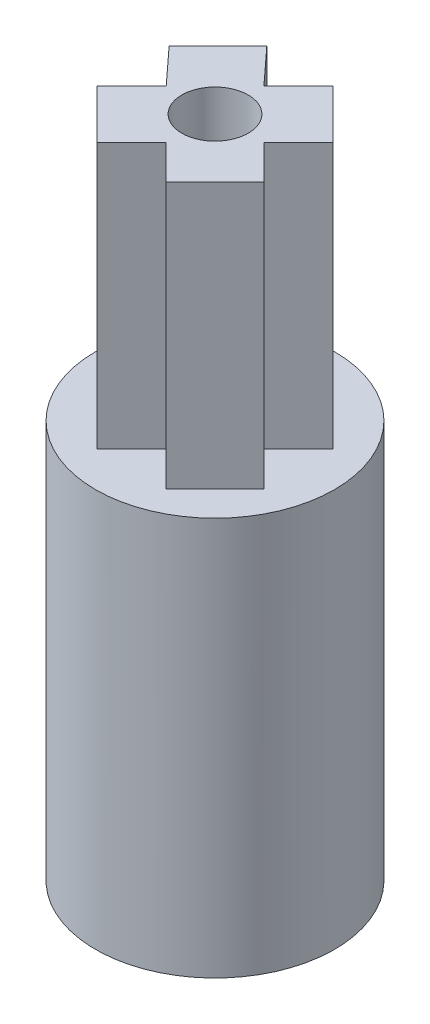
SolidWorks part; units mm, degrees
ref_plane "Front Plane" through (0, 0, 0) normal (0, 0, 1) x (1, 0, 0)
ref_plane "Top Plane" through (0, 0, 0) normal (0, 1, 0) x (1, 0, 0)
ref_plane "Right Plane" through (0, 0, 0) normal (1, 0, 0) x (0, 0, -1)
sketch "Sketch1" plane through (0, 0, 0) normal (0, 1, 0) x (1, 0, 0)
  circle A2 centre (0, 0) radius 5.715
  dimension "D3" = 11.43
extrude "Boss-Extrude1" add sketch "Sketch1" along normal blind 6.35
sketch "Sketch3" plane through (0, 0, 0) normal (0, -1, 0) x (-1, 0, 0)
  circle A0 centre (0, 0) radius 5.715
extrude "Boss-Extrude2" add sketch "Sketch3" along normal blind 12.7
sketch "Sketch4" plane through (0, -12.7, 0) normal (0, -1, 0) x (1, 0, 0)
  line L0 (0, 2.54) -> (-1.7961, 4.3361)
  line L1 (-2.54, -2.54) -> (2.54, -2.54) construction
  line L2 (-2.54, -2.54) -> (-2.54, 2.54) construction
  line L3 (-2.54, 2.54) -> (2.54, 2.54) construction
  line L4 (2.54, -2.54) -> (2.54, 2.54) construction
  line L5 (-2.54, -2.54) -> (2.54, 2.54) construction
  line L6 (-2.54, 2.54) -> (2.54, -2.54) construction
  line L7 (-2.54, 0) -> (-4.3361, 1.7961)
  line L8 (-4.3361, 1.7961) -> (-1.7961, 4.3361)
  line L9 (2.54, 0) -> (4.3361, -1.7961)
  line L10 (0, -2.54) -> (1.7961, -4.3361)
  line L11 (1.7961, -4.3361) -> (4.3361, -1.7961)
  line L12 (-2.54, 0) -> (-4.3361, -1.7961)
  line L13 (0, -2.54) -> (-1.7961, -4.3361)
  line L14 (-4.3361, -1.7961) -> (-1.7961, -4.3361)
  line L15 (2.54, 0) -> (4.3361, 1.7961)
  line L16 (1.7961, 4.3361) -> (4.3361, 1.7961)
  line L17 (0, 2.54) -> (1.7961, 4.3361)
  point P0 (0, 0)
  dimension "D1" = 2.54
  dimension "D2" = 5.08
  dimension "D3" = 5.08
  dimension "D4" = 8.6721
  dimension "D5" = 3.5921
  dimension "D6" = 3.5921
  dimension "D7" = 3.5921
  dimension "D8" = 3.5921
  dimension "D9" = 8.6721
  dimension "D10" = 0
  dimension "D11" = 3.5921
  dimension "D12" = 5.08
  dimension "D13" = 2.54
  dimension "D14" = 2.54
  dimension "D15" = 2.54
  dimension "D16" = 2.54
  dimension "D17" = 2.54
  dimension "D18" = 2.54
  dimension "D19" = 2.54
  dimension "D20" = 2.54
extrude "Cut-Extrude1" cut sketch "Sketch4" against normal blind 12.7
sketch "Sketch5" plane through (0, 6.35, 0) normal (0, 1, 0) x (1, 0, 0)
  line L0 (0, 2.5419) -> (-1.7372, 4.3949) construction
  line L1 (-2.54, -2.54) -> (2.54, -2.54) construction
  line L2 (-2.54, -2.54) -> (-2.54, 2.54) construction
  line L3 (-2.54, 2.54) -> (2.54, 2.54) construction
  line L4 (2.54, -2.54) -> (2.54, 2.54) construction
  line L5 (-2.54, -2.54) -> (2.54, 2.54) construction
  line L6 (-2.54, 2.54) -> (2.54, -2.54) construction
  line L7 (-2.54, 0.0019) -> (-4.2772, 1.8549) construction
  line L8 (-4.2772, 1.8549) -> (-1.7372, 4.3949) construction
  line L9 (2.54, 0) -> (4.3361, -1.7961) construction
  line L10 (0, -2.54) -> (1.7961, -4.3361) construction
  line L11 (1.7961, -4.3361) -> (4.3361, -1.7961) construction
  line L12 (-2.54, 0.0019) -> (-4.3358, -1.7945) construction
  line L13 (0, -2.54) -> (-1.7967, -4.3354) construction
  line L14 (-4.3358, -1.7945) -> (-1.7967, -4.3354) construction
  line L15 (2.54, 0) -> (4.3372, 1.7949) construction
  line L16 (1.7981, 4.3359) -> (4.3372, 1.7949) construction
  line L17 (0, 2.5419) -> (1.7981, 4.3359) construction
  line L18 (0, 2.3397) -> (1.6556, 3.9889)
  line L19 (-3.9887, -1.6499) -> (-1.6534, -3.9881)
  line L20 (-3.9181, 1.7234) -> (-1.5813, 4.0602)
  line L21 (0, -2.3368) -> (1.6524, -3.9892)
  line L22 (1.6524, -3.9892) -> (3.9892, -1.6524)
  line L23 (-2.3368, 0.0029) -> (-3.9887, -1.6499)
  line L24 (0, -2.3368) -> (-1.6534, -3.9881)
  line L25 (2.3368, 0) -> (3.9909, 1.6506)
  line L26 (0, 2.3397) -> (-1.5813, 4.0602)
  line L27 (-2.3368, 0.0029) -> (-3.9181, 1.7234)
  line L28 (1.6556, 3.9889) -> (3.9909, 1.6506)
  line L29 (2.3368, 0) -> (3.9892, -1.6524)
  point P0 (0, 0)
  dimension "D1" = 2.54
  dimension "D2" = 5.08
  dimension "D3" = 5.08
  dimension "D4" = 8.6721
  dimension "D5" = 3.5921
  dimension "D6" = 3.5921
  dimension "D7" = 3.5921
  dimension "D8" = 3.5921
  dimension "D9" = 8.6721
  dimension "D10" = 0
  dimension "D11" = 3.5921
  dimension "D12" = 5.08
  dimension "D13" = 2.54
  dimension "D14" = 2.54
  dimension "D15" = 2.54
  dimension "D16" = 2.54
  dimension "D17" = 2.54
  dimension "D18" = 2.54
  dimension "D19" = 2.54
  dimension "D20" = 2.54
extrude "Boss-Extrude3" add sketch "Sketch5" along normal blind 12.7
sketch "Sketch6" plane through (0, 19.05, 0) normal (0, 1, 0) x (1, 0, 0)
  circle A0 centre (0, 0) radius 1.5875
  dimension "D1" = 3.175
extrude "Cut-Extrude2" cut sketch "Sketch6" against normal through all
